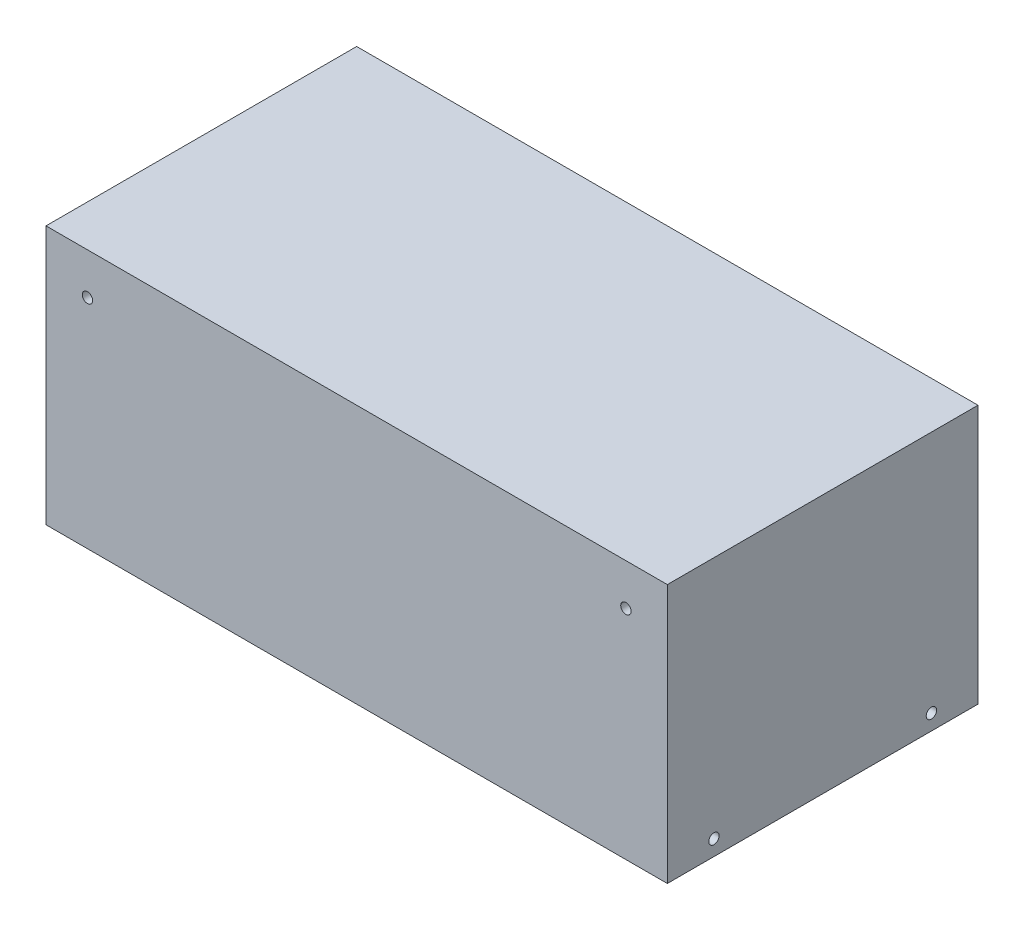
SolidWorks part; units mm, degrees
material "ABS PC"
ref_plane "Front Plane" through (0, 0, 0) normal (0, 0, 1) x (1, 0, 0)
ref_plane "Top Plane" through (0, 0, 0) normal (0, 1, 0) x (1, 0, 0)
ref_plane "Right Plane" through (0, 0, 0) normal (1, 0, 0) x (0, 0, -1)
sketch "Sketch1" plane through (0, 0, 0) normal (0, 1, 0) x (1, 0, 0)
  line L1 (150, -75) -> (-150, -75)
  line L2 (150, -75) -> (150, 75)
  line L3 (150, 75) -> (-150, 75)
  line L4 (-150, -75) -> (-150, 75)
  line L5 (150, -75) -> (-150, 75) construction
  line L6 (150, 75) -> (-150, -75) construction
  point P0 (0, 0)
  dimension "D1" = 300
  dimension "D2" = 150
extrude "Boss-Extrude1" add sketch "Sketch1" along normal blind 125
sketch "Sketch2" plane through (0, 0, 0) normal (0, -1, 0) x (1, 0, 0)
  line L0 (-150, 75) -> (150, 75) construction
  line L1 (135, -60) -> (-135, -60)
  line L2 (135, -60) -> (135, 60)
  line L3 (135, 60) -> (-135, 60)
  line L4 (-135, -60) -> (-135, 60)
  line L5 (135, -60) -> (-135, 60) construction
  line L6 (135, 60) -> (-135, -60) construction
  line L7 (150, 75) -> (150, -75) construction
  point P0 (0, 0)
  point P8 (150, 0)
  dimension "D1" = 15
  dimension "D2" = 15
extrude "Cut-Extrude1" cut sketch "Sketch2" against normal blind 110
sketch "Sketch4" plane through (150, 0, 0) normal (1, 0, 0) x (0, 0, -1)
  line L0 (-75, 0) -> (75, 0) construction
  line L1 (75, 125) -> (75, 0) construction
  line L5 (-75, 125) -> (-75, 0) construction
  circle A0 centre (-52.5, 7.5) radius 2.5
  circle A1 centre (52.5, 7.5) radius 2.5
  dimension "D3" = 5
  dimension "D4" = 5
  dimension "D1" = 7.5
  dimension "D2" = 22.5
  dimension "D5" = 7.5
  dimension "D6" = 22.5
extrude "Cut-Extrude5" cut sketch "Sketch4" against normal blind 350
sketch "Sketch6" plane through (0, 0, 75) normal (0, 0, 1) x (1, 0, 0)
  line L0 (-150, 125) -> (-150, 0) construction
  line L1 (-150, 125) -> (150, 125) construction
  line L2 (0, 140.9499) -> (0, -14.4188) construction
  circle A0 centre (-130, 105) radius 2.5
  circle A1 centre (130, 105) radius 2.5
  dimension "D1" = 5
  dimension "D2" = 20
  dimension "D3" = 20
extrude "Cut-Extrude6" cut sketch "Sketch6" against normal blind 175
fillet "Fillet1" radius 5 1 edges at (0, 110, -60)
fillet "Fillet2" radius 5 1 edges at (0, 110, 60)
fillet "Fillet3" radius 5 5 edges at (-135, 52.5, 60) (-135, 108.5355, 58.5355) (-135, 52.5, -60) (-135, 108.5355, -58.5355) (-135, 110, 0)
fillet "Fillet4" radius 5 5 edges at (135, 52.5, -60) (135, 108.5355, -58.5355) (135, 52.5, 60) (135, 108.5355, 58.5355) (135, 110, 0)
fillet "Fillet5" radius 2 8 edges at (-133.5355, 0, -58.5355) (-135, 0, 0) (-133.5355, 0, 58.5355) (0, 0, 60) (133.5355, 0, 58.5355) (135, 0, 0) (133.5355, 0, -58.5355) (0, 0, -60)
